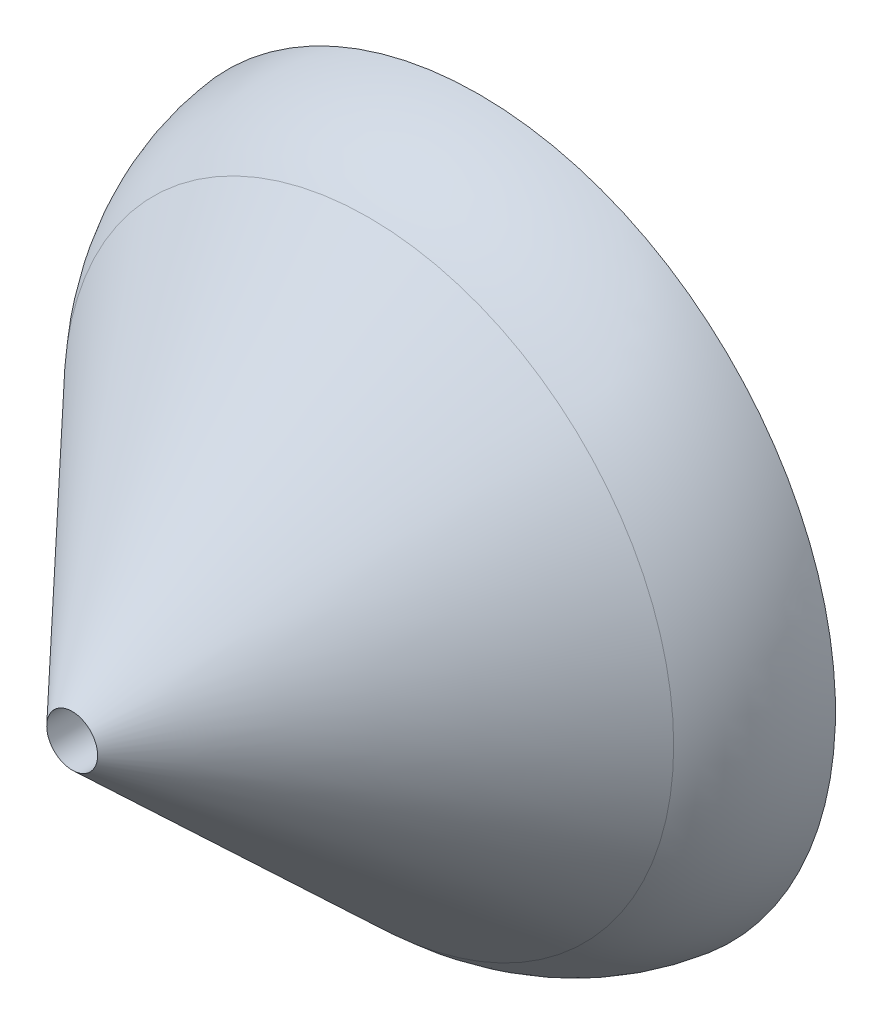
SolidWorks part; units mm, degrees
ref_plane "Front Plane" through (0, 0, 0) normal (1, 0, 0) x (0, 1, 0)
ref_plane "Top Plane" through (0, 0, 0) normal (0, 0, 1) x (0, 1, 0)
ref_plane "Right Plane" through (0, 0, 0) normal (0, 1, 0) x (-1, 0, 0)
sketch "Sketch2" plane through (0, 0, 0) normal (1, 0, 0) x (0, 1, 0)
  line L19 (0, 0) -> (0, 338.517) construction
  line L22 (-50.8, 0) -> (-50.8, 13.9605)
  line L23 (-50.8, 13.9605) -> (-42.6656, 22.5964)
  line L24 (-42.6656, 22.5964) -> (-6.35, 22.5964)
  line L25 (-6.35, 22.5964) -> (-6.35, 35.2964)
  line L26 (-6.35, 35.2964) -> (-30.7032, 35.2964)
  line L27 (-30.7032, 35.2964) -> (-6.35, 61.151)
  line L29 (-88.9, 13.9605) -> (-6.35, 101.6)
  line L34 (-88.9, 13.9605) -> (-88.9, 0)
  line L36 (-88.9, 0) -> (-50.8, 0)
  line L37 (-6.35, 101.6) -> (-6.35, 61.151)
  point P1 (-6.35, 85.0801)
  point P11 (-88.9, 21.5804)
  point P13 (-6.35, 80.0001)
  point P15 (-88.9, 38.8523)
  point P16 (-88.9, 13.9605)
  dimension "D1" = 88.9
  dimension "D2" = 50.8
  dimension "D3" = 12.7
  dimension "D4" = 12.7
  dimension "D5" = 12.7
  dimension "D6" = 101.6
revolve "Revolve1" add sketch "Sketch2" angle 360 about L19
fillet "Fillet1" radius 48.26 1 edges at (0, 88.9, 13.9605)
